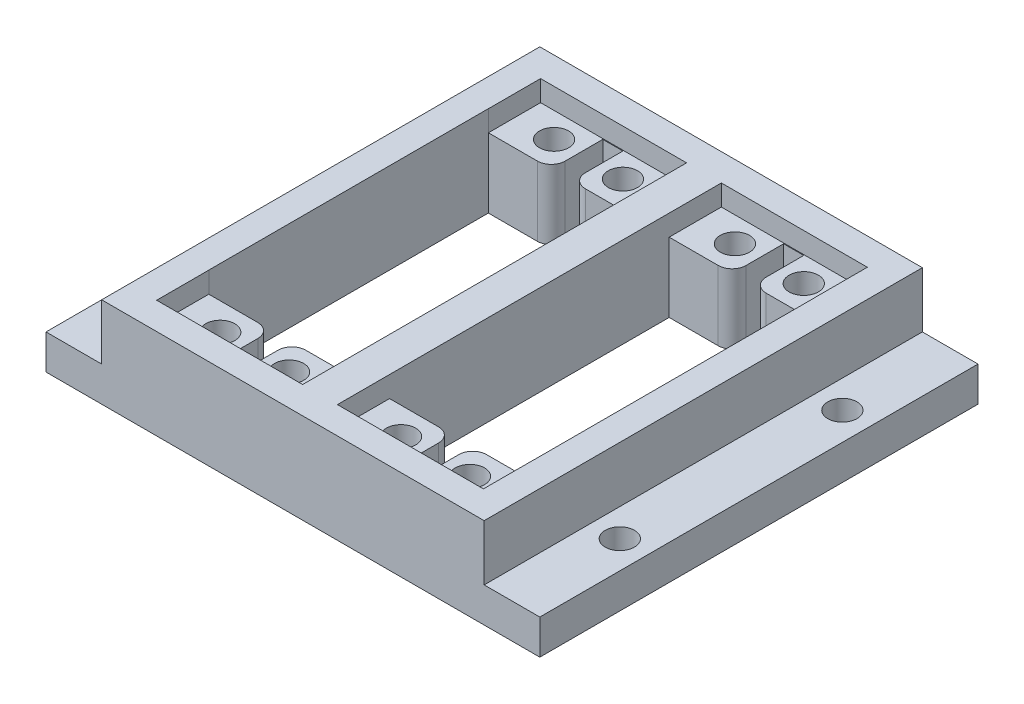
SolidWorks part; units mm, degrees
ref_plane "Front Plane" through (0, 0, 0) normal (0, 0, 1) x (1, 0, 0)
ref_plane "Top Plane" through (0, 0, 0) normal (0, 1, 0) x (1, 0, 0)
ref_plane "Right Plane" through (0, 0, 0) normal (1, 0, 0) x (0, 0, -1)
sketch "Sketch2" plane through (0, 0, 0) normal (0, 1, 0) x (1, 0, 0)
  line L0 (0, 0) -> (0, 31.5) construction
  line L1 (-27.5, -31.5) -> (27.5, -31.5)
  line L2 (-27.5, -31.5) -> (-27.5, 31.5)
  line L3 (-27.5, 31.5) -> (27.5, 31.5)
  line L4 (27.5, -31.5) -> (27.5, 31.5)
  line L5 (-27.5, -31.5) -> (27.5, 31.5) construction
  line L6 (-27.5, 31.5) -> (27.5, -31.5) construction
  line L7 (2.5, 24) -> (23.5, 24) construction
  line L8 (11.55, -27.5) -> (14.45, -27.5)
  line L9 (2.5, -20.1) -> (2.5, 20.1)
  line L10 (11.55, 27.5) -> (14.45, 27.5) construction
  line L11 (23.5, -27.5) -> (23.5, -26.9182)
  line L12 (16.45, 20.1) -> (23.5, 20.1)
  line L13 (11.55, 27.5) -> (14.45, 27.5)
  line L14 (11.55, 27.5) -> (11.55, 22.1)
  line L15 (11.55, 20.1) -> (14.45, 20.1) construction
  line L16 (14.45, 27.5) -> (14.45, 22.1)
  line L17 (2.5, 20.1) -> (9.55, 20.1)
  line L18 (2.5, 20.1) -> (2.5, -20.1)
  line L20 (23.5, 20.1) -> (23.5, -20.1)
  line L21 (23.5, 26.9182) -> (23.5, 27.5)
  line L22 (16.45, -20.1) -> (23.5, -20.1)
  line L23 (14.45, -27.5) -> (14.45, -22.1)
  line L24 (11.55, -27.5) -> (14.45, -27.5)
  line L25 (11.55, -27.5) -> (11.55, -22.1)
  line L26 (2.5, -20.1) -> (9.55, -20.1)
  line L27 (23.5, -20.1) -> (23.5, 20.1)
  line L28 (-16.45, 20.1) -> (-23.5, 20.1)
  line L29 (-14.45, 27.5) -> (-14.45, 22.1)
  line L30 (-11.55, 27.5) -> (-14.45, 27.5)
  line L31 (-11.55, 27.5) -> (-11.55, 22.1)
  line L32 (-2.5, 20.1) -> (-9.55, 20.1)
  line L33 (-23.5, 20.1) -> (-23.5, -20.1)
  line L34 (-2.5, -20.1) -> (-2.5, 20.1)
  line L35 (-14.45, -27.5) -> (-14.45, -22.1)
  line L36 (-16.45, -20.1) -> (-23.5, -20.1)
  line L37 (-2.5, -20.1) -> (-9.55, -20.1)
  line L38 (-11.55, -27.5) -> (-11.55, -22.1)
  line L39 (-11.55, -27.5) -> (-14.45, -27.5)
  line L40 (31.5, 31.5) -> (31.5, -31.5) construction
  line L41 (27.5, 31.5) -> (35.5, 31.5)
  line L42 (27.5, 31.5) -> (27.5, -31.5)
  line L43 (27.5, -31.5) -> (35.5, -31.5)
  line L44 (35.5, 31.5) -> (35.5, -31.5)
  line L45 (0, 0) -> (75.3399, 0) construction
  line L46 (-27.5, -31.5) -> (-35.5, -31.5)
  line L47 (-35.5, 31.5) -> (-35.5, -31.5)
  line L48 (-27.5, 31.5) -> (-35.5, 31.5)
  line L49 (-27.5, 31.5) -> (-27.5, -31.5)
  circle A0 centre (8.05, 24) radius 2.1
  circle A1 centre (17.95, 24) radius 2.1
  circle A2 centre (8.05, 24) radius 3.5 construction
  circle A3 centre (17.95, 24) radius 3.5 construction
  circle A4 centre (13, 9.8) radius 7.238
  circle A5 centre (8.05, -24) radius 2.1
  circle A6 centre (17.95, -24) radius 2.1
  arc A7 (16.45, -20.1) -> (14.45, -22.1) centre (16.45, -22.1) ccw
  arc A8 (11.55, -22.1) -> (9.55, -20.1) centre (9.55, -22.1) ccw
  arc A9 (16.45, 20.1) -> (14.45, 22.1) centre (16.45, 22.1) cw
  arc A10 (9.55, 20.1) -> (11.55, 22.1) centre (9.55, 22.1) ccw
  circle A11 centre (-13, 9.8) radius 7.238
  circle A12 centre (-8.05, 24) radius 2.1
  circle A13 centre (-17.95, 24) radius 2.1
  arc A14 (-16.45, 20.1) -> (-14.45, 22.1) centre (-16.45, 22.1) ccw
  arc A15 (-9.55, 20.1) -> (-11.55, 22.1) centre (-9.55, 22.1) cw
  circle A16 centre (-8.05, -24) radius 2.1
  circle A17 centre (-17.95, -24) radius 2.1
  arc A18 (-16.45, -20.1) -> (-14.45, -22.1) centre (-16.45, -22.1) cw
  arc A19 (-11.55, -22.1) -> (-9.55, -20.1) centre (-9.55, -22.1) cw
  circle A20 centre (31.5, 16) radius 2.1
  circle A21 centre (31.5, -16) radius 2.1
  circle A22 centre (-31.5, -16) radius 2.1
  circle A23 centre (-31.5, 16) radius 2.1
  point P0 (0, 0)
  point P28 (13, 9.8)
  dimension "D8" = 4.2
  dimension "D11" = 7.4
  dimension "D13" = 2
  dimension "D15" = 4.2
  dimension "D1" = 55
  dimension "D2" = 63
  dimension "D3" = 2.5
  dimension "D4" = 4
  dimension "D5" = 4
  dimension "D6" = 4
  dimension "D7" = 3.5
  dimension "D9" = 9.9
  dimension "D10" = 5.55
  dimension "D12" = 14.2
  dimension "D14" = 8
  dimension "D16" = 16
extrude "Boss-Extrude1" add sketch "Sketch2" along normal blind 13 contours L1 L4 L3 L2 A19 L38 L39 L35 A18 L36 L33 L28 A14 L29 L30 L31 A15 L32 L34 L37 A17 A16 A12 L17 A10 L14 L13 L16 A9 L12 L20 L22 A7 L23 L8 L25 A8 L26 L9 region at (0, 0, 0)
sketch "Sketch3" plane through (0, 13, 0) normal (0, 1, 0) x (1, 0, 0)
  line L0 (0, 0) -> (12.8645, 0) construction
  line L1 (2.5, 20.1) -> (23.4917, 20.1)
  line L2 (2.5, 20.1) -> (2.5, 27.6)
  line L3 (2.5, 27.6) -> (23.4917, 27.6)
  line L4 (23.4917, 20.1) -> (23.4917, 27.6)
  line L5 (0, 0) -> (0, 6.2924) construction
  line L6 (2.5, -27.6) -> (23.4917, -27.6)
  line L7 (23.4917, -20.1) -> (23.4917, -27.6)
  line L8 (2.5, -20.1) -> (23.4917, -20.1)
  line L9 (2.5, -20.1) -> (2.5, -27.6)
  line L10 (-2.5, -20.1) -> (-2.5, -27.6)
  line L11 (-2.5, -20.1) -> (-23.4917, -20.1)
  line L12 (-23.4917, -20.1) -> (-23.4917, -27.6)
  line L13 (-2.5, -27.6) -> (-23.4917, -27.6)
  line L14 (-2.5, 27.6) -> (-23.4917, 27.6)
  line L15 (-23.4917, 20.1) -> (-23.4917, 27.6)
  line L16 (-2.5, 20.1) -> (-23.4917, 20.1)
  line L17 (-2.5, 20.1) -> (-2.5, 27.6)
  dimension "D1" = 7.5
extrude "Cut-Extrude1" cut sketch "Sketch3" against normal blind 3
extrude "Boss-Extrude2" add sketch "Sketch2<3>" along normal blind 5 contours L2 L48 L47 L46 A22 A23 | L44 L41 L4 L43 A20 A21 region at (-31.5, 0, 0) region at (31.5, 0, 0)
sketch "Sketch2<3>" plane through (0, 0, 0) normal (0, 1, 0) x (1, 0, 0) same geometry as "Sketch2"
sketch "Sketch7" plane through (0, 13, 0) normal (0, 1, 0) x (1, 0, 0)
  line L1 (-35.5, 31.5) -> (35.5, 31.5)
  line L2 (-35.5, 31.5) -> (-35.5, -31.5)
  line L3 (-35.5, -31.5) -> (35.5, -31.5)
  line L4 (35.5, 31.5) -> (35.5, -31.5)
  line L5 (0, 0) -> (61.619, 0) construction
  line L8 (-23.4917, 20.1) -> (-2.5, 20.1)
  line L9 (-23.4917, 20.1) -> (-23.4917, -20.1)
  line L10 (-23.4917, -20.1) -> (-2.5, -20.1)
  line L11 (-2.5, 20.1) -> (-2.5, -20.1)
  line L12 (2.5, 20.1) -> (23.5, 20.1)
  line L13 (2.5, 20.1) -> (2.5, -20.1)
  line L14 (2.5, -20.1) -> (23.5, -20.1)
  line L15 (23.5, 20.1) -> (23.5, -20.1)
  circle A0 centre (-17.95, 24) radius 2.1
  circle A1 centre (-8.05, 24) radius 2.1
  circle A2 centre (8.05, 24) radius 2.1
  circle A3 centre (17.95, 24) radius 2.1
  circle A4 centre (-13, 9.8) radius 7.238
  circle A5 centre (13, 9.8) radius 7.238
  circle A6 centre (31.5, 16) radius 2.1
  circle A7 centre (-31.5, 16) radius 2.1
  circle A8 centre (31.5, -16) radius 2.1
  circle A9 centre (17.95, -24) radius 2.1
  circle A10 centre (8.05, -24) radius 2.1
  circle A11 centre (-17.95, -24) radius 2.1
  circle A12 centre (-8.05, -24) radius 2.1
  circle A13 centre (-31.5, -16) radius 2.1
